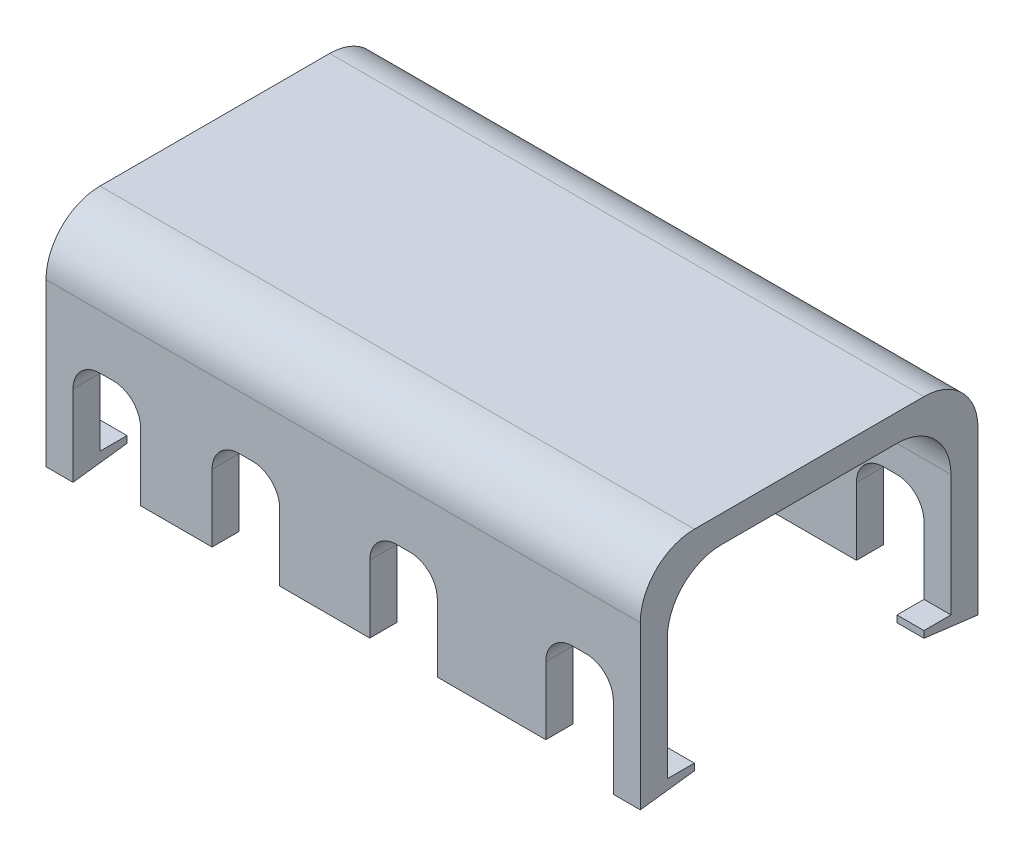
SolidWorks part; units mm, degrees
ref_plane "Plano frontal" through (0, 0, 0) normal (0, 0, 1) x (1, 0, 0)
ref_plane "Plano superior" through (0, 0, 0) normal (0, 1, 0) x (1, 0, 0)
ref_plane "Plano direito" through (0, 0, 0) normal (1, 0, 0) x (0, 0, -1)
sketch "Esboço1" plane through (0, 0, 0) normal (0, 1, 0) x (1, 0, 0)
  line L1 (-22, -12.5) -> (22, -12.5)
  line L2 (-22, -12.5) -> (-22, 12.5)
  line L3 (-22, 12.5) -> (22, 12.5)
  line L4 (22, -12.5) -> (22, 12.5)
  line L5 (-22, -12.5) -> (22, 12.5) construction
  line L6 (-22, 12.5) -> (22, -12.5) construction
  point P0 (0, 0)
  dimension "D1" = 44
  dimension "D2" = 25
extrude "Ressalto-extrusão1" add sketch "Esboço1" along normal mid plane 15
shell "Casca1" thickness 2 removed face at (0, -7.5, 0) removed face at (-22, 0, 0) removed face at (22, 0, 0)
sketch "Esboço2" plane through (0, 0, 12.5) normal (0, 0, 1) x (1, 0, 0)
  line L0 (22, 7.5) -> (22, -7.5) construction
  line L5 (-9.7033, -14.5) -> (-4.7033, -14.5)
  line L6 (-9.7033, -14.5) -> (-9.7033, -0.5)
  line L7 (-22, -7.5) -> (22, -7.5) construction
  line L8 (-20, -14.5) -> (-15, -14.5)
  line L9 (-20, -14.5) -> (-20, -0.5)
  line L10 (-20, -0.5) -> (-15, -0.5)
  line L11 (-15, -14.5) -> (-15, -0.5)
  line L12 (-20, -14.5) -> (-15, -0.5) construction
  line L13 (-20, -0.5) -> (-15, -14.5) construction
  line L14 (-22, 7.5) -> (-22, -7.5) construction
  line L15 (-9.7033, -0.5) -> (-4.7033, -0.5)
  line L16 (-4.7033, -14.5) -> (-4.7033, -0.5)
  line L17 (-9.7033, -14.5) -> (-4.7033, -0.5) construction
  line L18 (-9.7033, -0.5) -> (-4.7033, -14.5) construction
  line L19 (1.9702, -14.5) -> (6.9702, -14.5)
  line L20 (1.9702, -14.5) -> (1.9702, -0.5)
  line L21 (1.9702, -0.5) -> (6.9702, -0.5)
  line L22 (6.9702, -14.5) -> (6.9702, -0.5)
  line L23 (1.9702, -14.5) -> (6.9702, -0.5) construction
  line L24 (1.9702, -0.5) -> (6.9702, -14.5) construction
  line L25 (15, -14.5) -> (20, -14.5)
  line L26 (15, -14.5) -> (15, -0.5)
  line L27 (15, -0.5) -> (20, -0.5)
  line L28 (20, -14.5) -> (20, -0.5)
  line L29 (15, -14.5) -> (20, -0.5) construction
  line L30 (15, -0.5) -> (20, -14.5) construction
  point P0 (-17.5, -7.5)
  point P9 (-7.2033, -7.5)
  point P14 (4.4702, -7.5)
  point P19 (17.5, -7.5)
  dimension "D2" = 5
  dimension "D3" = 7
  dimension "D1" = 2
  dimension "D4" = 2
extrude "Corte-extrusão1" cut sketch "Esboço2" against normal through all
fillet "Filete1" radius 2 16 edges at (15, -0.5, 11.5) (15, -0.5, -11.5) (20, -0.5, 11.5) (20, -0.5, -11.5) (1.9702, -0.5, 11.5) (1.9702, -0.5, -11.5) (6.9702, -0.5, 11.5) (6.9702, -0.5, -11.5) (-9.7033, -0.5, 11.5) (-9.7033, -0.5, -11.5) (-4.7033, -0.5, 11.5) (-4.7033, -0.5, -11.5) (-15, -0.5, 11.5) (-15, -0.5, -11.5) (-20, -0.5, -11.5) (-20, -0.5, 11.5)
fillet "Filete2" radius 4 4 edges at (0, 7.5, -12.5) (0, 7.5, 12.5) (0, 5.5, 10.5) (0, 5.5, -10.5)
sketch "Esboço3" plane through (-22, 0, 0) normal (1, 0, 0) x (0, 0, -1)
  line L0 (10.5, -7.5) -> (8.5, -7.5)
  line L2 (12.5, -8.5) -> (12.5, -7.5)
  line L3 (0, 5.5) -> (0, -5.9035) construction
  line L4 (6.5, 5.5) -> (-6.5, 5.5) construction
  line L8 (10.5, -7.5) -> (12.5, -7.5)
  line L10 (8.5, -7.5) -> (8.5, -8)
  line L11 (8.5, -8) -> (12.5, -8.5)
  line L12 (-8.5, -8) -> (-12.5, -8.5)
  line L13 (-8.5, -7.5) -> (-8.5, -8)
  line L14 (-10.5, -7.5) -> (-12.5, -7.5)
  line L15 (-12.5, -8.5) -> (-12.5, -7.5)
  line L16 (-10.5, -7.5) -> (-8.5, -7.5)
  dimension "D1" = 2
  dimension "D2" = 1
  dimension "D3" = 0.5
extrude "Ressalto-extrusão2" add sketch "Esboço3" along normal blind 2
mirror "Espelhar1" about plane through (0, 0, 0) normal (1, 0, 0) of "Ressalto-extrusão2"
move or copy body "Corpo-Converter em corpo de malha1" [suppressed] bodies to move or copy 104 copy no translate (0, 0, 0) parameters "D1"=0, "D2"=0, "D3"=0
